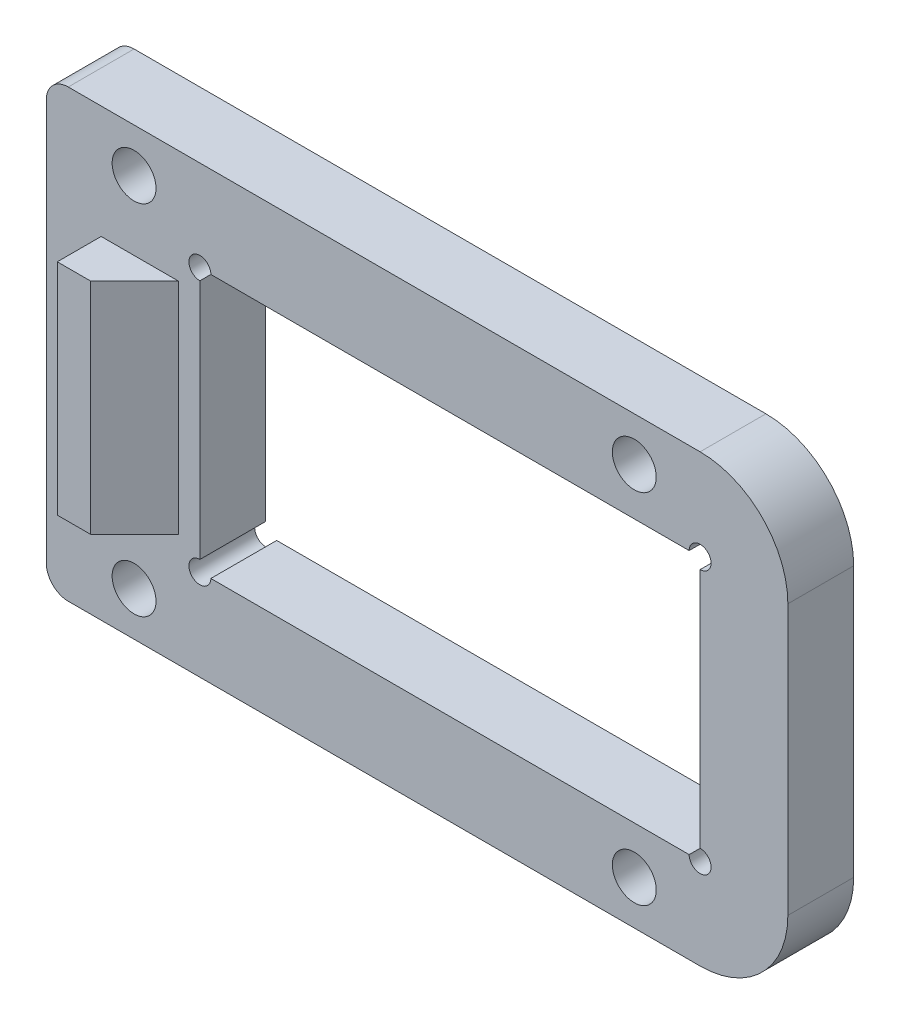
SolidWorks part; units mm, degrees
ref_plane "Front Plane" through (0, 0, 0) normal (0, 0, 1) x (1, 0, 0)
ref_plane "Top Plane" through (0, 0, 0) normal (0, 1, 0) x (1, 0, 0)
ref_plane "Right Plane" through (0, 0, 0) normal (1, 0, 0) x (0, 0, -1)
sketch "Sketch2" plane through (0, 0, 0) normal (0, 0, 1) x (1, 0, 0)
  line L3 (51.486, 0.793) -> (17.686, 0.793)
  line L6 (42.486, 10.943) -> (42.486, 6.793)
  line L7 (46.486, 10.943) -> (46.486, 6.793)
  line L8 (22.686, 10.943) -> (26.686, 10.943)
  line L13 (17.686, 10.943) -> (51.486, 10.943)
  line L14 (17.686, 10.943) -> (17.686, 0.793)
  line L15 (17.686, 0.793) -> (51.486, 0.793)
  line L16 (51.486, 10.943) -> (51.486, 0.793)
  line L17 (25.186, 6.793) -> (46.986, 6.793)
  line L18 (24.686, 6.293) -> (24.686, 0.793)
  line L19 (24.686, 0.793) -> (47.486, 0.793)
  line L20 (47.486, 6.293) -> (47.486, 0.793)
  circle A1 centre (44.486, 8.943) radius 1
  arc A3 (25.186, 6.793) -> (24.686, 6.293) centre (24.686, 6.793) ccw
  arc A4 (47.486, 6.293) -> (46.986, 6.793) centre (47.486, 6.793) ccw
  circle A5 centre (21.686, 8.943) radius 1
  dimension "D5" = 33.8
  dimension "D2" = 2
  dimension "D3" = 4
  dimension "D4" = 2
  dimension "D8" = 2
  dimension "D9" = 2
  dimension "D10" = 7
  dimension "D12" = 22.8
  dimension "D13" = 6
extrude "Boss-Extrude1" add sketch "Sketch2" along normal blind 3 contours A4 L20 L3 L16 L13 L7 L17 | A1 | L6 L17 L7 L13 A1 | A3 L17 L6 L13 L8 L14 L15 L18
mirror "Mirror1" about plane through (0, 0.793, 3) normal (0, -1, 0) of bodies 101
sketch "Sketch3" plane through (0, 0, 3) normal (0, 0, 1) x (1, 0, 0)
  line L1 (20.186, 5.793) -> (23.7012, 5.793)
  line L2 (20.186, 5.793) -> (20.186, -4.207)
  line L3 (20.186, -4.207) -> (23.7012, -4.207)
  line L4 (23.7012, 5.793) -> (23.7012, -4.207)
  line L5 (51.486, 10.943) -> (17.686, 10.943)
  line L7 (51.486, -9.357) -> (17.686, -9.357)
  line L8 (17.686, 10.943) -> (17.686, -9.357)
  point P10 (20.186, 0.793)
  point P11 (17.686, 0.793)
  dimension "D1" = 10
  dimension "D2" = 3.5153
  dimension "D3" = 0
  dimension "D4" = 2.5
extrude "Boss-Extrude2" add sketch "Sketch3" along normal blind 2 contours L4 L1 L2 L3
chamfer "Chamfer1" distance 2 angle 45 1 edges at (23.7012, 0.793, 5)
fillet "Fillet1" radius 4 2 edges at (51.486, 10.943, 1.5) (51.486, -9.357, 1.5)
fillet "Fillet2" radius 1 2 edges at (17.686, 10.943, 1.5) (17.686, -9.357, 1.5)
